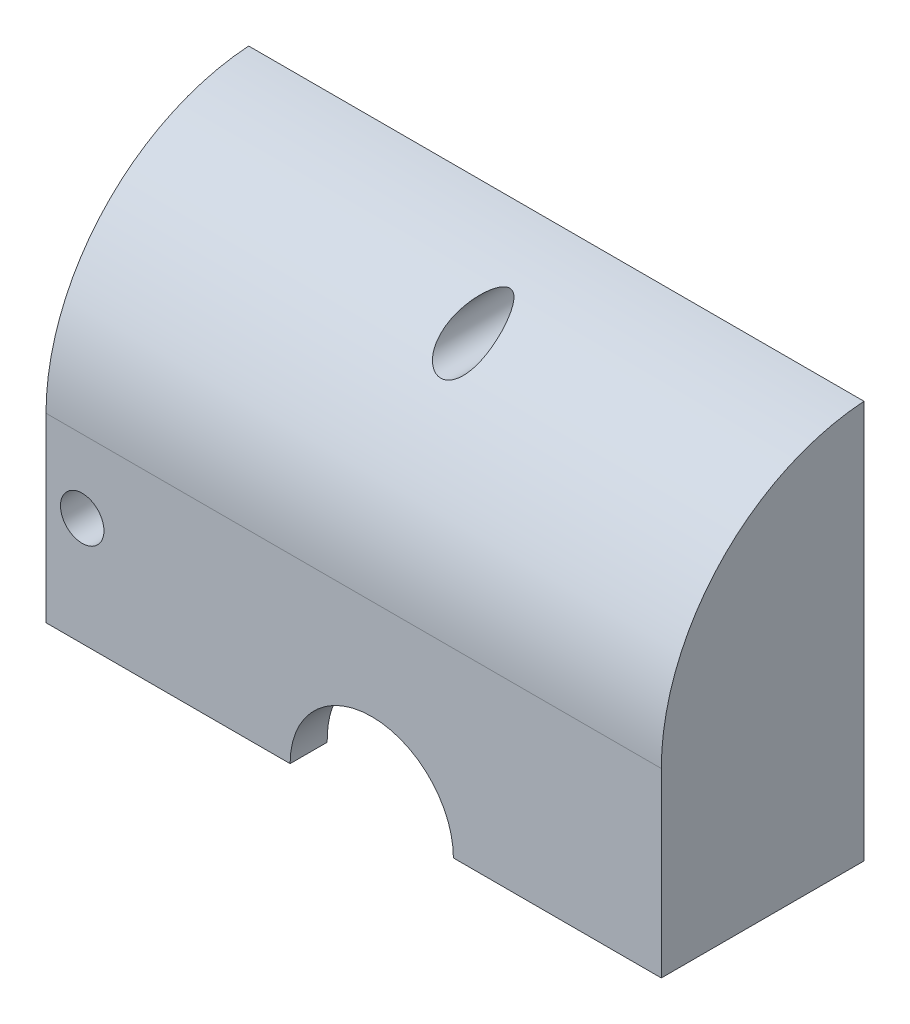
SolidWorks part; units mm, degrees
ref_plane "Front Plane" through (0, 0, 0) normal (0, 0, 1) x (1, 0, 0)
ref_plane "Top Plane" through (0, 0, 0) normal (0, 1, 0) x (1, 0, 0)
ref_plane "Right Plane" through (0, 0, 0) normal (1, 0, 0) x (0, 0, -1)
sketch "Sketch1" plane through (0, 0, 0) normal (0, 0, 1) x (1, 0, 0)
  line L1 (0, 0) -> (90, 0)
  line L2 (0, 0) -> (0, 110)
  line L3 (0, 110) -> (90, 110)
  line L4 (90, 0) -> (90, 110)
  dimension "D1" = 110
  dimension "D2" = 90
extrude "Boss-Extrude1" add sketch "Sketch1" along normal blind 28
sketch "Sketch2" plane through (0, 0, 0) normal (-1, 0, 0) x (0, 0, 1)
  line L0 (0, 99.7487) -> (0, 20.2513) construction
  line L1 (0, 110) -> (0, 0) construction
  line L2 (0, 20.2513) -> (14, 16.5) construction
  line L3 (14, 16.5) -> (14, 103.5) construction
  line L4 (14, 103.5) -> (0, 99.7487) construction
  line L5 (25.5, 60) -> (0, 60) construction
  line L6 (28, 0) -> (0, 0) construction
  line L7 (25.5, 48.72) -> (14, 16.5) construction
  line L8 (25.5, 71.28) -> (25.5, 48.72) construction
  line L9 (25.5, 71.28) -> (14, 103.5) construction
  line L10 (0, 99.7487) -> (14, 103.5)
  line L11 (14, 103.5) -> (14, 16.5)
  line L12 (14, 16.5) -> (0, 20.2513)
  line L13 (0, 20.2513) -> (0, 99.7487)
  dimension "D1" = 105
  dimension "D2" = 105
  dimension "D3" = 87
  dimension "D4" = 43.5
  dimension "D5" = 60
  dimension "D6" = 14
  dimension "D7" = 22.56
  dimension "D8" = 25.5
fillet "Fillet2" radius 30 2 edges at (45, 0, 28) (45, 110, 28)
sketch "Sketch3" plane through (0, 0, 0) normal (0, 0, -1) x (-1, 0, 0)
  line L0 (0, 110) -> (0, 0) construction
  line L1 (-90, 110) -> (0, 110) construction
  line L2 (0, 0) -> (-90, 0) construction
  circle A0 centre (-45, 105) radius 1.5
  circle A1 centre (-45, 5) radius 1.5
  circle A2 centre (-5, 70) radius 1.5
  circle A3 centre (-5, 40) radius 1.5
  dimension "D1" = 3
  dimension "D2" = 3
  dimension "D3" = 45
  dimension "D8" = 5
  dimension "D4" = 5
  dimension "D5" = 5
  dimension "D6" = 40
  dimension "D7" = 40
extrude "Cut-Extrude1" cut sketch "Sketch3" against normal through all
sketch "Sketch4" plane through (0, 0, 28) normal (0, 0, 1) x (1, 0, 0)
  circle A0 centre (45, 105) radius 3
  circle A1 centre (45, 5) radius 3
  circle A2 centre (5, 70) radius 3
  circle A3 centre (45, 105) radius 1.5 construction
  circle A4 centre (45, 5) radius 1.5 construction
  circle A5 centre (5, 40) radius 3
  circle A6 centre (5, 40) radius 1.5 construction
  circle A7 centre (5, 70) radius 1.5 construction
  dimension "D1" = 6
extrude "Cut-Extrude4" cut sketch "Sketch4" against normal blind 26
sketch "Sketch5" plane through (0, 0, 0) normal (0, 0, -1) x (-1, 0, 0)
  line L0 (-8.5, 55) -> (-81.5, 55) construction
  line L1 (-81.5, 11.5) -> (-8.5, 11.5)
  line L2 (-81.5, 11.5) -> (-81.5, 98.5)
  line L3 (-81.5, 98.5) -> (-8.5, 98.5)
  line L4 (-8.5, 11.5) -> (-8.5, 98.5)
  line L5 (-45, 98.5) -> (-45, 11.5) construction
  line L6 (0, 0) -> (-90, 0) construction
  line L8 (0, 99.7487) -> (0, 20.2513) construction
  dimension "D1" = 87
  dimension "D2" = 73
  dimension "D3" = 55
  dimension "D4" = 45
extrude "Cut-Extrude5" cut sketch "Sketch5" along normal blind 13.7 draft 15 from offset 13.7 offset against normal yes
sketch "Sketch8" plane through (0, 0, 13.7) normal (0, 0, -1) x (-1, 0, 0)
  line L0 (-81.5, 98.5) -> (-81.5, 11.5)
  line L1 (-81.5, 11.5) -> (-8.5, 11.5)
  line L2 (-8.5, 11.5) -> (-8.5, 98.5)
  line L3 (-8.5, 98.5) -> (-81.5, 98.5)
extrude "Cut-Extrude8" cut sketch "Sketch8" against normal blind 11.8 draft 70
sketch "Sketch9" plane through (0, 0, 25.5) normal (0, 0, -1) x (-1, 0, 0)
  line L0 (-49.0798, 43.9202) -> (-40.9202, 43.9202) construction
  line L2 (-40.9202, 43.9202) -> (-40.9202, 66.0798) construction
  circle A0 centre (-45.0002, 55.0002) radius 11.28
  dimension "D1" = 22.56
  dimension "D2" = 11.08
  dimension "D3" = 4.08
extrude "Cut-Extrude9" cut sketch "Sketch9" against normal blind 61.8 from offset 30
fillet "Fillet19" radius 20 4 edges at (10.3355, 13.3355, 6.85) (10.3355, 96.6645, 6.85) (79.6645, 96.6645, 6.85) (79.6645, 13.3355, 6.85)
sketch "Sketch11" plane through (0, 0, 0) normal (0, 0, -1) x (-1, 0, 0)
  line L0 (-90, 55) -> (0, 55) construction
  line L1 (-90, 0) -> (-90, 110) construction
  line L2 (0, 110) -> (0, 0) construction
  line L3 (0, 0) -> (-90, 0) construction
  line L4 (-45, 110) -> (-45, 0) construction
  line L5 (-90, 110) -> (0, 110) construction
  dimension "D1" = 55
  dimension "D2" = 45
ref_plane "Plane1" through (0, 55, 0) normal (0, 1, 0) x (1, 0, 0)
sketch "Sketch13" plane through (0, 0, 0) normal (0, 0, -1) x (-1, 0, 0)
  line L9 (-90, 55) -> (0, 55)
  line L10 (-90, 55) -> (-90, 0)
  line L11 (-90, 0) -> (0, 0)
  line L12 (0, 55) -> (0, 0)
extrude "Cut-Extrude10" cut sketch "Sketch13" against normal through all
sketch "Sketch14" plane through (0, 0, 0) normal (-1, 0, 0) x (0, 0, 1)
  line L1 (6.5, 58.5) -> (0, 58.5)
  line L2 (0, 20.2513) -> (0, 99.7487) construction
  line L3 (6.5, 51.5) -> (0, 51.5)
  line L4 (10, 55) -> (10, 45) construction
  line L5 (15.4, 55) -> (-15.4, 55) construction
  line L6 (0, 58.5) -> (0, 51.5)
  arc A0 (6.5, 51.5) -> (6.5, 58.5) centre (6.5, 55) ccw
  dimension "D3" = 7
  dimension "D1" = 10
  dimension "D2" = 10
extrude "Cut-Extrude12" cut sketch "Sketch14" against normal up to vertex (12.1709 mm away) up to point (12.1709, 75.5106, 0)
sketch "Sketch15" plane through (0, 0, 0) normal (0, 0, -1) x (-1, 0, 0)
  line L0 (-90, 110) -> (0, 110) construction
  line L1 (-90, 55) -> (-85, 55)
  line L2 (-90, 55) -> (-90, 110)
  line L3 (-90, 110) -> (-85, 110)
  line L4 (-85, 55) -> (-85, 110)
  dimension "D1" = 5
extrude "Cut-Extrude13" cut sketch "Sketch15" against normal through all
equation "\".mm\"=16"
